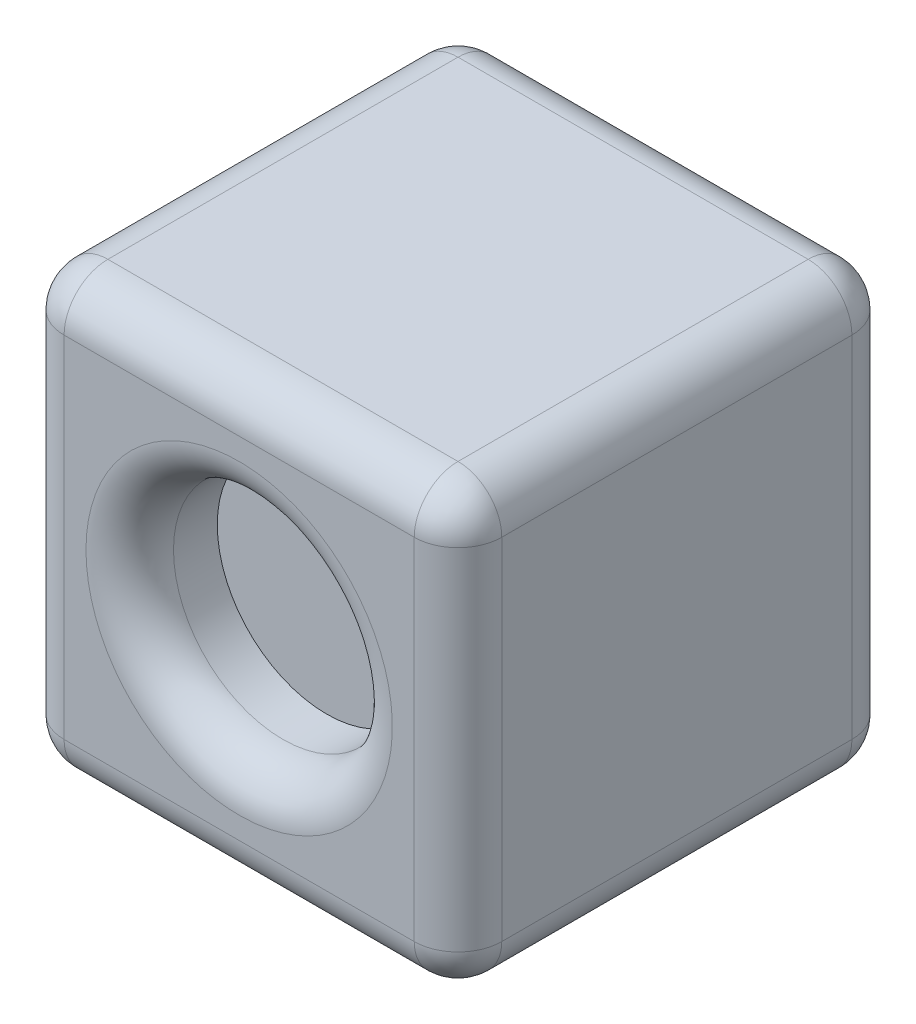
SolidWorks part; units mm, degrees
material "Brass"
ref_plane "Front Plane" through (0, 0, 0) normal (0, 0, 1) x (1, 0, 0)
ref_plane "Top Plane" through (0, 0, 0) normal (0, 1, 0) x (1, 0, 0)
ref_plane "Right Plane" through (0, 0, 0) normal (1, 0, 0) x (0, 0, -1)
sketch "Sketch1" plane through (0, 0, 0) normal (0, 0, 1) x (1, 0, 0)
  line L1 (-50, -50) -> (50, -50)
  line L2 (-50, -50) -> (-50, 50)
  line L3 (-50, 50) -> (50, 50)
  line L4 (50, -50) -> (50, 50)
  line L5 (-50, -50) -> (50, 50) construction
  line L6 (-50, 50) -> (50, -50) construction
  point P0 (0, 0)
  dimension "D1" = 100
  dimension "D2" = 100
extrude "Boss-Extrude1" add sketch "Sketch1" along normal blind 100
sketch "Sketch2" plane through (0, 0, 100) normal (0, 0, 1) x (1, 0, 0)
  circle A0 centre (0, 0) radius 25
  dimension "D1" = 50
extrude "Cut-Extrude1" cut sketch "Sketch2" against normal blind 20 contours A0
sketch "Sketch6" plane through (-50, 0, 0) normal (-1, 0, 0) x (0, 0, 1)
  line L0 (0, 50) -> (100, -50)
  line L1 (100, 50) -> (100, -50) construction
  line L2 (75.9808, -15) -> (75.9808, 15)
  line L3 (75.9808, 15) -> (50, 30)
  line L4 (50, 30) -> (24.0192, 15)
  line L5 (24.0192, 15) -> (24.0192, -15)
  line L6 (24.0192, -15) -> (50, -30)
  line L7 (50, -30) -> (75.9808, -15)
  circle A0 centre (50, 0) radius 25.9808 construction
  dimension "D1" = 30
extrude "Cut-Extrude3" cut sketch "Sketch6" against normal blind 20 contours L6 L7 L0 L4 L5 | L0 L7 L2 L3 L4 region at (-50, 7.9743, 58.453) region at (-50, -7.9743, 41.547)
chamfer "Chamfer1" distance 5 angle 45 6 edges at (-50, -22.5, 62.9904) (-50, -22.5, 37.0096) (-50, 0, 24.0192) (-50, 22.5, 37.0096) (-50, 22.5, 62.9904) (-50, 0, 75.9808)
fillet "Fillet1" radius 10 1 edges at (25, 0, 100)
fillet "Fillet2" radius 10 7 edges at (-50, 50, 50) (0, -50, 0) (50, -50, 50) (0, 50, 100) (-50, 0, 100) (0, -50, 100) (-50, -50, 50)
fillet "Fillet3" radius 10 11 edges at (47.0711, -47.0711, 2.9289) (-47.0711, -47.0711, 2.9289) (-50, 0, 0) (-47.0711, 47.0711, 0) (47.0711, -47.0711, 97.0711) (50, 47.0711, 97.0711) (50, 5, 0) (-45, 0, 75.9808) (5, 50, 0) (50, 50, 45) (50, 0, 100)
